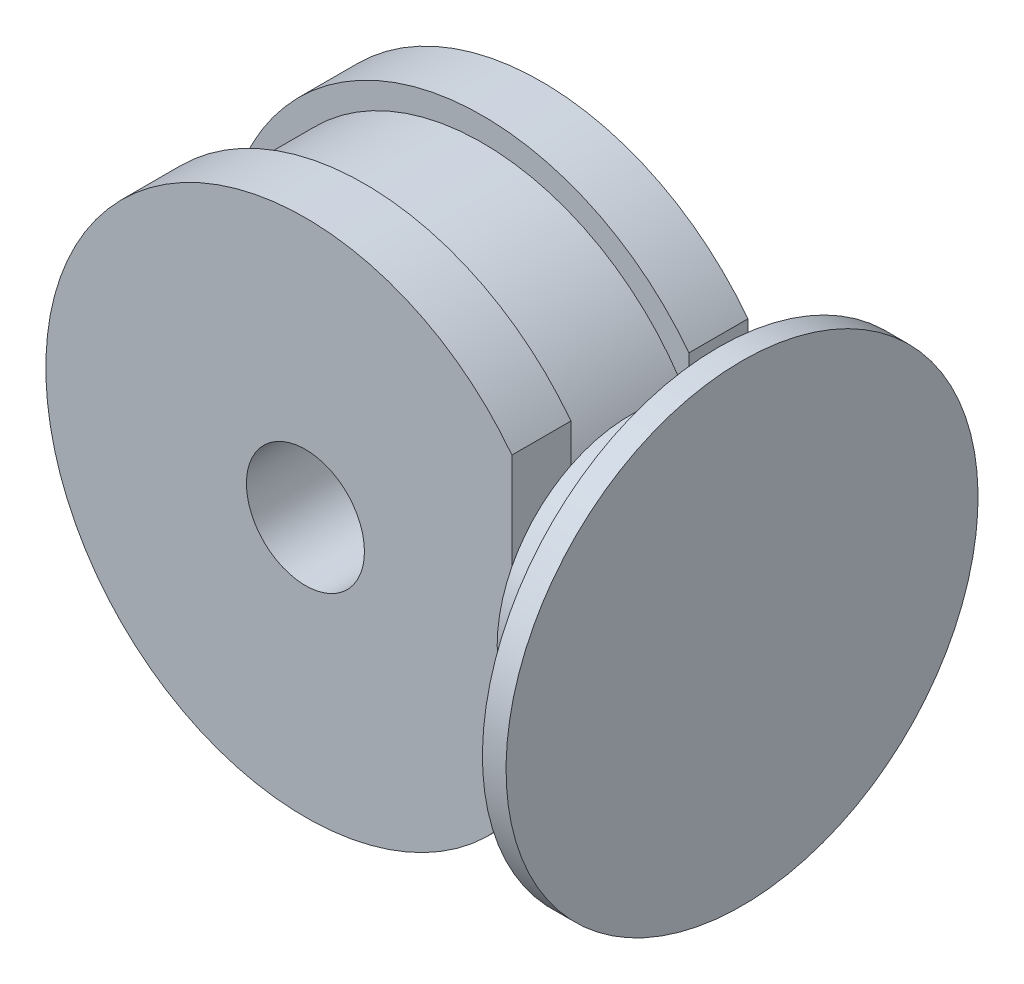
SolidWorks part; units mm, degrees
ref_plane "Plan de face" through (0, 0, 0) normal (0, 0, 1) x (1, 0, 0)
ref_plane "Plan de dessus" through (0, 0, 0) normal (0, 1, 0) x (1, 0, 0)
ref_plane "Plan de droite" through (0, 0, 0) normal (1, 0, 0) x (0, 0, -1)
sketch "Esquisse1" plane through (0, 0, 0) normal (0, 0, 1) x (1, 0, 0)
  circle A0 centre (0, 0) radius 44
  dimension "D1" = 88
extrude "Boss.-Extru.1" add sketch "Esquisse1" along normal blind 10
sketch "Esquisse2" plane through (0, 0, 10) normal (0, 0, 1) x (1, 0, 0)
  circle A0 centre (0, 0) radius 40
  dimension "D1" = 80
extrude "Boss.-Extru.2" add sketch "Esquisse2" along normal blind 20
sketch "Esquisse3" plane through (0, 0, 30) normal (0, 0, 1) x (1, 0, 0)
  circle A0 centre (0, 0) radius 44
extrude "Boss.-Extru.3" add sketch "Esquisse3" along normal blind 10
sketch "Esquisse5" plane through (0, 0, 40) normal (0, 0, 1) x (1, 0, 0)
  line L1 (35, 44.0697) -> (67.4724, 44.0697)
  line L2 (35, 44.0697) -> (35, -50.6619)
  line L3 (35, -50.6619) -> (67.4724, -50.6619)
  line L4 (67.4724, 44.0697) -> (67.4724, -50.6619)
  dimension "D1" = 35
extrude "Enlèv. mat.-Extru.2" cut sketch "Esquisse5" against normal through all
sketch "Esquisse4" plane through (0, 0, 40) normal (0, 0, 1) x (1, 0, 0)
  circle A0 centre (0, 0) radius 10
  dimension "D1" = 20
extrude "Enlèv. mat.-Extru.1" cut sketch "Esquisse4" against normal through all
ref_point "Point1"
sketch "Sketch1" plane through (35, 0, 0) normal (1, 0, 0) x (0, 0, -1)
  circle A0 centre (-20, 0) radius 22.5
extrude "Boss-Extrude1" add sketch "Sketch1" along normal blind 15
sketch "Sketch2" plane through (50, 0, 0) normal (1, 0, 0) x (0, 0, -1)
  circle A0 centre (-20, 0) radius 40
  dimension "D1" = 80
extrude "Boss-Extrude2" add sketch "Sketch2" along normal blind 4
